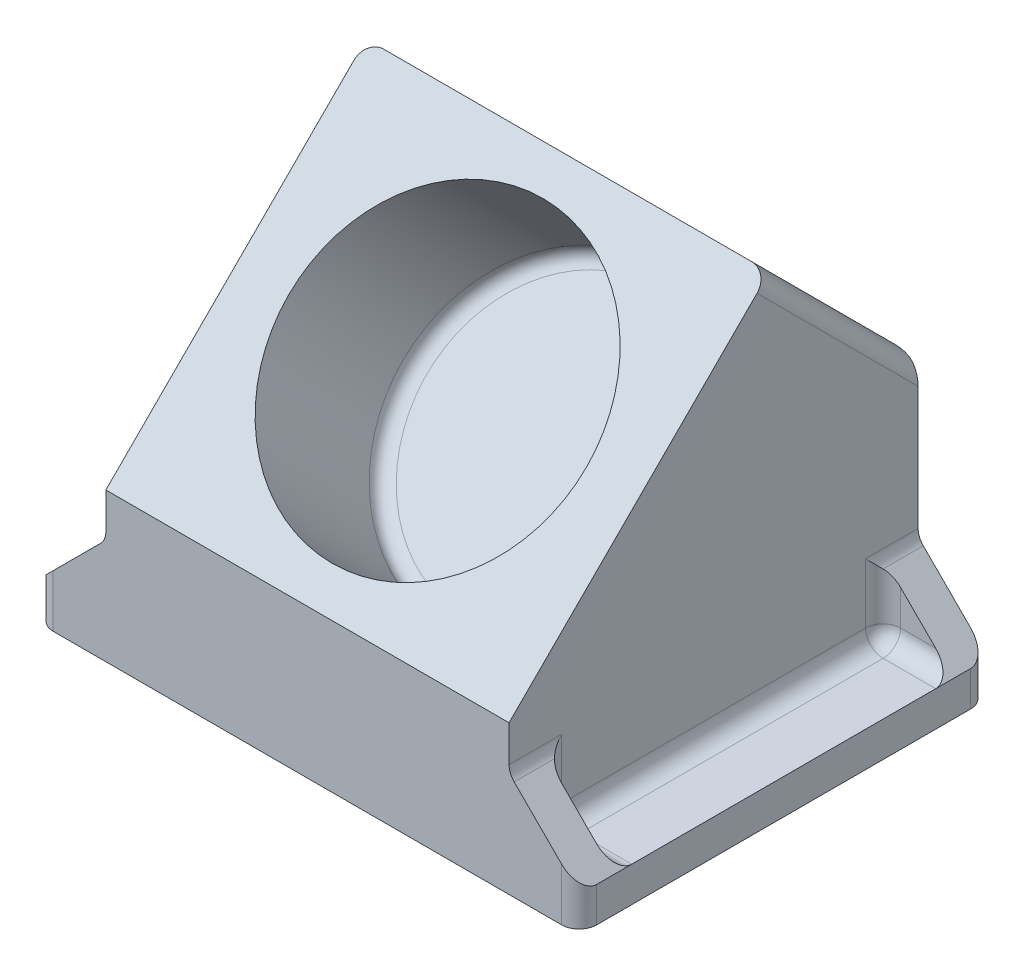
SolidWorks part; units mm, degrees
ref_plane "Front Plane" through (0, 0, 0) normal (0, 0, 1) x (1, 0, 0)
ref_plane "Top Plane" through (0, 0, 0) normal (0, 1, 0) x (1, 0, 0)
ref_plane "Right Plane" through (0, 0, 0) normal (1, 0, 0) x (0, 0, -1)
sketch "Esquisse2" plane through (0, 0, 0) normal (1, 0, 0) x (0, 0, -1)
  line L0 (-58.3363, 0) -> (58.3363, 0)
  line L2 (15.9099, 116.6726) -> (58.3363, 74.2462)
  line L3 (58.3363, 74.2462) -> (58.3363, 0)
  line L4 (-58.3363, 42.4264) -> (-58.3363, 0)
  line L5 (-51.2652, 49.4975) -> (-15.9099, 14.1421)
  line L6 (-15.9099, 14.1421) -> (44.1942, 74.2462)
  line L7 (44.1942, 74.2462) -> (8.8388, 109.6016)
  line L8 (-58.3363, 42.4264) -> (-51.2652, 49.4975)
  line L9 (-51.2652, 49.4975) -> (8.8388, 109.6016)
  line L10 (8.8388, 109.6016) -> (15.9099, 116.6726)
  line L11 (44.1942, 74.2462) -> (58.3363, 74.2462) construction
  line L12 (-15.9099, 14.1421) -> (-15.9099, 0) construction
  point P3 (0, 0)
  dimension "D1" = 135
  dimension "D2" = 85
  dimension "D3" = 10
  dimension "D4" = 50
extrude "Boss.-Extru.1" add sketch "Esquisse2" along normal mid plane 115 contours L10 L7 L6 L5 L8 L4 L0 L3 L2 | L9 L5 L6 L7 region at (0, 32.5091, -11.8864) region at (0, 61.8718, 3.5355)
sketch "Esquisse3" plane through (0, 50.3814, 50.3814) normal (0, 0.7071, 0.7071) x (1, 0, 0)
  line L0 (0, -1.25) -> (0, 83.75) construction
  circle A0 centre (0, 41.25) radius 42.5
  point P4 (0, 41.25)
extrude "Enlèv. mat.-Extru.1" cut sketch "Esquisse3" against normal blind 50 contours A0
sketch "Esquisse4" plane through (0, 0, 0) normal (0, -1, 0) x (1, 0, 0)
  line L0 (57.5, 58.3363) -> (-57.5, 58.3363) construction
  line L1 (-77.5, 58.3363) -> (77.5, 58.3363)
  line L2 (-77.5, 58.3363) -> (-77.5, -58.3363)
  line L3 (-77.5, -58.3363) -> (77.5, -58.3363)
  line L4 (77.5, 58.3363) -> (77.5, -58.3363)
  line L5 (57.5, -58.3363) -> (-57.5, -58.3363) construction
  line L6 (-57.5, 58.3363) -> (-57.5, -58.3363) construction
  line L7 (-77.5, -48.3363) -> (-57.5, -48.3363)
  line L8 (-57.5, -48.3363) -> (-57.5, 48.3363)
  line L9 (-57.5, 48.3363) -> (-77.5, 48.3363)
  line L10 (-77.5, 48.3363) -> (-77.5, -48.3363)
  line L11 (57.5, 48.3363) -> (77.5, 48.3363)
  line L12 (57.5, 58.3363) -> (57.5, -58.3363) construction
  line L13 (77.5, 48.3363) -> (77.5, -48.3363)
  line L14 (77.5, -48.3363) -> (57.5, -48.3363)
  line L15 (57.5, -48.3363) -> (57.5, 48.3363)
  point P4 (0, 58.3363)
  point P20 (57.5, 0)
  line M5 (-57.5, 58.3363) -> (-57.5, -58.3363)
  line M7 (57.5, -58.3363) -> (57.5, 58.3363)
  dimension "D1" = 20
  dimension "D2" = 10
extrude "Boss.-Extru.2" add sketch "Esquisse4" against normal blind 10 contours L3 L4 L1 L2
chamfer "Chanfrein1" distance 20 angle 45 2 edges at (57.5, 10, 0) (-57.5, 10, 0)
extrude "Enlèv. mat.-Extru.2" cut sketch "Esquisse4<3>" against normal up to next from offset 10 contours L9 L2 L7 M5 | L14 L4 L11 M7 region at (-67.5, 0, 0) region at (67.5, 0, 0) offset against normal yes
sketch "Esquisse4<3>" plane through (0, 0, 0) normal (0, -1, 0) x (1, 0, 0) same geometry as "Esquisse4"
fillet "Congé3" radius 5 14 edges at (57.5, 10, 0) (-57.5, 10, 0) (-57.5, 20, 48.3363) (-67.5, 10, 48.3363) (-57.5, 30, 53.3363) (-57.5, 30, -53.3363) (-57.5, 20, -48.3363) (-67.5, 10, -48.3363) (57.5, 30, -53.3363) (57.5, 20, -48.3363) (67.5, 10, -48.3363) (57.5, 30, 53.3363) (67.5, 10, 48.3363) (57.5, 20, 48.3363)
fillet "Congé1" radius 4 1 edges at (0, 14.1421, 15.9099)
fillet "Congé2" radius 5 7 edges at (0, 74.2462, -58.3363) (-57.5, 95.4594, -37.1231) (57.5, 95.4594, -37.1231) (-77.5, 5, -58.3363) (77.5, 5, -58.3363) (77.5, 5, 58.3363) (-77.5, 5, 58.3363) tangent propagation no
